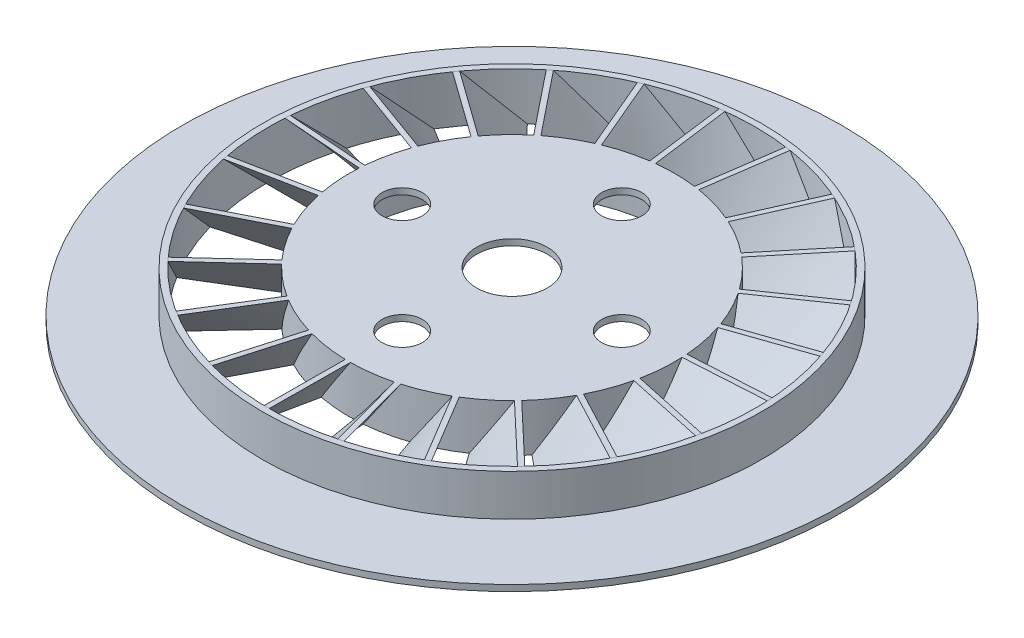
SolidWorks part; units mm, degrees
ref_plane "Front Plane" through (0, 0, 0) normal (0, 0, 1) x (1, 0, 0)
ref_plane "Top Plane" through (0, 0, 0) normal (0, 1, 0) x (1, 0, 0)
ref_plane "Right Plane" through (0, 0, 0) normal (1, 0, 0) x (0, 0, -1)
sketch "Sketch1" plane through (0, 0, 0) normal (0, 1, 0) x (1, 0, 0)
  circle A0 centre (0, 0) radius 33.25
  circle A1 centre (0, 0) radius 34.0882
  circle A2 centre (0, 0) radius 45
  circle A3 centre (0, 0) radius 22.25
  circle A4 centre (0, 0) radius 21.4118
  dimension "D1" = 66.5
  dimension "D2" = 0.8382
  dimension "D3" = 90
  dimension "D4" = 44.5
  dimension "D5" = 0.8382
extrude "Boss-Extrude1" add sketch "Sketch1" along normal blind 6.5 contours A1 A0 region at (-33.9918, 0, 0)
extrude "Boss-Extrude2" add sketch "Sketch1<3>" along normal blind 0.8382 contours A2 A1 region at (-43.7272, 0, 0)
sketch "Sketch1<3>" plane through (0, 0, 0) normal (0, 1, 0) x (1, 0, 0) same geometry as "Sketch1"
extrude "Boss-Extrude3" add sketch "Sketch1<4>" along normal blind 6.5 separate body contours A3 A4 region at (-21.6207, 0, 0)
sketch "Sketch1<4>" plane through (0, 0, 0) normal (0, 1, 0) x (1, 0, 0) same geometry as "Sketch1"
extrude "Boss-Extrude4" add sketch "Sketch1<5>" along normal blind 0.7 contours A4 region at (0, 0, 0)
sketch "Sketch1<5>" plane through (0, 0, 0) normal (0, 1, 0) x (1, 0, 0) same geometry as "Sketch1"
sketch "Sketch2" plane through (0, 0, 0) normal (0, -1, 0) x (1, 0, 0)
  line L0 (-31.9208, 9.3073) -> (-21.3278, 6.3393)
  line L1 (-33.2482, 0.35) -> (-22.2472, 0.35)
  line L2 (-33.2482, -0.35) -> (-22.2472, -0.35)
  line L3 (-32.1097, 8.6332) -> (-21.5167, 5.6652)
  line L4 (-28.226, 17.5743) -> (-18.8266, 11.8584)
  line L5 (-28.5897, 16.9762) -> (-19.1903, 11.2603)
  line L6 (-22.4378, 24.5378) -> (-14.9291, 16.498)
  line L7 (-22.9494, 24.0601) -> (-15.4407, 16.0202)
  line L8 (-14.9856, 29.6816) -> (-9.9244, 19.914)
  line L9 (-15.6071, 29.3595) -> (-10.5459, 19.592)
  line L10 (-6.4219, 32.624) -> (-4.1837, 21.8531)
  line L11 (-7.1072, 32.4815) -> (-4.869, 21.7107)
  line L12 (2.6181, 33.1468) -> (1.8674, 22.1715)
  line L13 (1.9198, 33.1945) -> (1.169, 22.2193)
  line L14 (11.4639, 31.2112) -> (7.7799, 20.8455)
  line L15 (10.8043, 31.4456) -> (7.1204, 21.0799)
  line L16 (19.4595, 26.9609) -> (13.1155, 17.9735)
  line L17 (18.8876, 27.3646) -> (12.5436, 18.3772)
  line L18 (26.0119, 20.711) -> (17.4783, 13.7685)
  line L19 (25.5701, 21.254) -> (17.0366, 14.3115)
  line L20 (30.635, 12.9251) -> (20.5449, 8.5423)
  line L21 (30.3561, 13.5671) -> (20.266, 9.1844)
  line L22 (32.9861, 4.1806) -> (22.0877, 2.6826)
  line L23 (32.8908, 4.874) -> (21.9924, 3.3761)
  line L24 (32.8908, -4.874) -> (21.9924, -3.3761)
  line L25 (32.9861, -4.1806) -> (22.0877, -2.6826)
  line L26 (30.3561, -13.5671) -> (20.266, -9.1844)
  line L27 (30.635, -12.9251) -> (20.5449, -8.5423)
  line L28 (25.5701, -21.254) -> (17.0366, -14.3115)
  line L29 (26.0119, -20.711) -> (17.4783, -13.7685)
  line L30 (18.8876, -27.3646) -> (12.5436, -18.3772)
  line L31 (19.4595, -26.9609) -> (13.1155, -17.9735)
  line L32 (10.8043, -31.4456) -> (7.1204, -21.0799)
  line L33 (11.4639, -31.2112) -> (7.7799, -20.8455)
  line L34 (1.9198, -33.1945) -> (1.169, -22.2193)
  line L35 (2.6181, -33.1468) -> (1.8674, -22.1715)
  line L36 (-7.1072, -32.4815) -> (-4.869, -21.7107)
  line L37 (-6.4219, -32.624) -> (-4.1837, -21.8531)
  line L38 (-15.6071, -29.3595) -> (-10.5459, -19.592)
  line L39 (-14.9856, -29.6816) -> (-9.9244, -19.914)
  line L40 (-22.9494, -24.0601) -> (-15.4407, -16.0202)
  line L41 (-22.4378, -24.5378) -> (-14.9291, -16.498)
  line L42 (-28.5897, -16.9762) -> (-19.1903, -11.2603)
  line L43 (-28.226, -17.5743) -> (-18.8266, -11.8584)
  line L44 (-32.1097, -8.6332) -> (-21.5167, -5.6652)
  line L45 (-31.9208, -9.3073) -> (-21.3278, -6.3393)
  circle A0 centre (0, 0) radius 33.25 construction
  circle A1 centre (0, 0) radius 22.25
  arc A2 (-21.3278, 6.3393) -> (-21.5167, 5.6652) centre (0, 0) ccw
  arc A3 (-18.8266, 11.8584) -> (-19.1903, 11.2603) centre (0, 0) ccw
  circle A5 centre (0, 0) radius 22.25 construction
  arc A6 (-31.9208, 9.3073) -> (-32.1097, 8.6332) centre (0, 0) ccw
  arc A7 (-28.226, 17.5743) -> (-28.5897, 16.9762) centre (0, 0) ccw
  arc A8 (-22.4378, 24.5378) -> (-22.9494, 24.0601) centre (0, 0) ccw
  arc A9 (-14.9291, 16.498) -> (-15.4407, 16.0202) centre (0, 0) ccw
  arc A10 (-9.9244, 19.914) -> (-10.5459, 19.592) centre (0, 0) ccw
  arc A11 (-14.9856, 29.6816) -> (-15.6071, 29.3595) centre (0, 0) ccw
  arc A12 (-6.4219, 32.624) -> (-7.1072, 32.4815) centre (0, 0) ccw
  arc A13 (-4.1837, 21.8531) -> (-4.869, 21.7107) centre (0, 0) ccw
  arc A14 (1.8674, 22.1715) -> (1.169, 22.2193) centre (0, 0) ccw
  arc A15 (2.6181, 33.1468) -> (1.9198, 33.1945) centre (0, 0) ccw
  arc A16 (11.4639, 31.2112) -> (10.8043, 31.4456) centre (0, 0) ccw
  arc A17 (7.7799, 20.8455) -> (7.1204, 21.0799) centre (0, 0) ccw
  arc A18 (13.1155, 17.9735) -> (12.5436, 18.3772) centre (0, 0) ccw
  arc A19 (19.4595, 26.9609) -> (18.8876, 27.3646) centre (0, 0) ccw
  arc A20 (26.0119, 20.711) -> (25.5701, 21.254) centre (0, 0) ccw
  arc A21 (17.4783, 13.7685) -> (17.0366, 14.3115) centre (0, 0) ccw
  arc A22 (20.5449, 8.5423) -> (20.266, 9.1844) centre (0, 0) ccw
  arc A23 (30.635, 12.9251) -> (30.3561, 13.5671) centre (0, 0) ccw
  arc A24 (32.9861, 4.1806) -> (32.8908, 4.874) centre (0, 0) ccw
  arc A25 (22.0877, 2.6826) -> (21.9924, 3.3761) centre (0, 0) ccw
  arc A26 (21.9924, -3.3761) -> (22.0877, -2.6826) centre (0, 0) ccw
  arc A27 (32.8908, -4.874) -> (32.9861, -4.1806) centre (0, 0) ccw
  arc A28 (-22.2472, 0.35) -> (-22.2472, -0.35) centre (0, 0) ccw
  arc A29 (-33.2482, 0.35) -> (-33.2482, -0.35) centre (0, 0) ccw
  arc A30 (-21.5167, -5.6652) -> (-21.3278, -6.3393) centre (0, 0) ccw
  arc A31 (-32.1097, -8.6332) -> (-31.9208, -9.3073) centre (0, 0) ccw
  arc A32 (-19.1903, -11.2603) -> (-18.8266, -11.8584) centre (0, 0) ccw
  arc A33 (-28.5897, -16.9762) -> (-28.226, -17.5743) centre (0, 0) ccw
  arc A34 (-22.9494, -24.0601) -> (-22.4378, -24.5378) centre (0, 0) ccw
  arc A35 (-15.4407, -16.0202) -> (-14.9291, -16.498) centre (0, 0) ccw
  arc A36 (-10.5459, -19.592) -> (-9.9244, -19.914) centre (0, 0) ccw
  arc A37 (-15.6071, -29.3595) -> (-14.9856, -29.6816) centre (0, 0) ccw
  arc A38 (-7.1072, -32.4815) -> (-6.4219, -32.624) centre (0, 0) ccw
  arc A39 (-4.869, -21.7107) -> (-4.1837, -21.8531) centre (0, 0) ccw
  arc A40 (1.169, -22.2193) -> (1.8674, -22.1715) centre (0, 0) ccw
  arc A41 (1.9198, -33.1945) -> (2.6181, -33.1468) centre (0, 0) ccw
  arc A42 (10.8043, -31.4456) -> (11.4639, -31.2112) centre (0, 0) ccw
  arc A43 (7.1204, -21.0799) -> (7.7799, -20.8455) centre (0, 0) ccw
  arc A44 (12.5436, -18.3772) -> (13.1155, -17.9735) centre (0, 0) ccw
  arc A45 (18.8876, -27.3646) -> (19.4595, -26.9609) centre (0, 0) ccw
  arc A46 (25.5701, -21.254) -> (26.0119, -20.711) centre (0, 0) ccw
  arc A47 (17.0366, -14.3115) -> (17.4783, -13.7685) centre (0, 0) ccw
  arc A48 (20.266, -9.1844) -> (20.5449, -8.5423) centre (0, 0) ccw
  arc A49 (30.3561, -13.5671) -> (30.635, -12.9251) centre (0, 0) ccw
  point P106 (0, 0)
  dimension "D3" = 0.7
  dimension "D1" = 0
  dimension "D4" = 23
sketch "Sketch3" plane through (0, 6.5, 0) normal (0, 1, 0) x (1, 0, 0)
  line L0 (0, 0) -> (-32.6054, -6.5152) construction
  line L1 (0, 0) -> (-15.6581, 0) construction
  line L2 (-21.8846, -4.016) -> (-32.6722, -6.1716)
  line L3 (-21.7474, -4.7025) -> (-32.535, -6.8581)
  line L4 (-22.1565, 2.0373) -> (-33.1257, 2.8721)
  line L5 (-22.2097, 1.3393) -> (-33.1788, 2.1741)
  line L6 (-20.7853, 7.9395) -> (-31.1225, 11.7028)
  line L7 (-21.0247, 7.2817) -> (-31.3619, 11.045)
  line L8 (-17.8724, 13.2529) -> (-26.811, 19.6656)
  line L9 (-18.2805, 12.6841) -> (-27.219, 19.0968)
  line L10 (-13.6341, 17.5833) -> (-20.511, 26.1698)
  line L11 (-14.1805, 17.1457) -> (-21.0574, 25.7322)
  line L12 (-8.3846, 20.6097) -> (-12.6899, 30.7332)
  line L13 (-9.0288, 20.3358) -> (-13.3341, 30.4592)
  line L14 (-2.5132, 22.1076) -> (-3.9276, 33.0172)
  line L15 (-3.2074, 22.0176) -> (-4.6218, 32.9272)
  line L16 (3.5445, 21.9659) -> (5.126, 32.8525)
  line L17 (2.8518, 22.0665) -> (4.4332, 32.9531)
  line L18 (9.3394, 20.195) -> (13.7994, 30.2513)
  line L19 (8.6995, 20.4788) -> (13.1595, 30.5351)
  line L20 (14.4416, 16.9264) -> (21.4494, 25.4064)
  line L21 (13.902, 17.3723) -> (20.9098, 25.8524)
  line L22 (18.4728, 12.4024) -> (27.5085, 18.6773)
  line L23 (18.0735, 12.9774) -> (27.1093, 19.2523)
  line L24 (21.1339, 6.9586) -> (31.5275, 10.563)
  line L25 (20.9045, 7.6199) -> (31.2982, 11.2244)
  line L26 (22.2276, 0.9987) -> (33.2083, 1.6653)
  line L27 (22.1852, 1.6974) -> (33.1659, 2.364)
  line L28 (21.6728, -5.0353) -> (32.4261, -7.356)
  line L29 (21.8204, -4.351) -> (32.5738, -6.6717)
  line L30 (19.5106, -10.6958) -> (29.239, -15.8316)
  line L31 (19.8374, -10.0768) -> (29.5658, -15.2126)
  line L32 (15.9014, -15.563) -> (23.8835, -23.1332)
  line L33 (16.3831, -15.0551) -> (24.3652, -22.6252)
  line L34 (11.1129, -19.2761) -> (16.7565, -28.719)
  line L35 (11.7137, -18.917) -> (17.3574, -28.3599)
  line L36 (5.5001, -21.5595) -> (8.3869, -32.1749)
  line L37 (6.1756, -21.3758) -> (9.0623, -31.9912)
  line L38 (-0.5205, -22.2439) -> (-0.6048, -33.2445)
  line L39 (0.1795, -22.2493) -> (0.0952, -33.2499)
  line L40 (-6.5025, -21.2786) -> (-9.5516, -31.8485)
  line L41 (-5.83, -21.4726) -> (-8.8791, -32.0425)
  line L42 (-12.0023, -18.7352) -> (-17.7901, -28.0905)
  line L43 (-11.407, -19.1035) -> (-17.1948, -28.4588)
  line L44 (-16.6119, -14.8023) -> (-24.7091, -22.2491)
  line L45 (-16.1381, -15.3175) -> (-24.2352, -22.7644)
  line L46 (-19.9895, -9.7715) -> (-29.7956, -14.7576)
  line L47 (-19.6722, -10.3955) -> (-29.4783, -15.3816)
  circle A0 centre (0, 0) radius 33.25 construction
  circle A1 centre (0, 0) radius 22.25 construction
  arc A2 (-32.6722, -6.1716) -> (-32.535, -6.8581) centre (0, 0) ccw
  arc A3 (-21.8846, -4.016) -> (-21.7474, -4.7025) centre (0, 0) ccw
  arc A4 (-22.1565, 2.0373) -> (-22.2097, 1.3393) centre (0, 0) ccw
  arc A5 (-33.1257, 2.8721) -> (-33.1788, 2.1741) centre (0, 0) ccw
  arc A6 (-20.7853, 7.9395) -> (-21.0247, 7.2817) centre (0, 0) ccw
  arc A7 (-31.1225, 11.7028) -> (-31.3619, 11.045) centre (0, 0) ccw
  arc A8 (-17.8724, 13.2529) -> (-18.2805, 12.6841) centre (0, 0) ccw
  arc A9 (-26.811, 19.6656) -> (-27.219, 19.0968) centre (0, 0) ccw
  arc A10 (-13.6341, 17.5833) -> (-14.1805, 17.1457) centre (0, 0) ccw
  arc A11 (-20.511, 26.1698) -> (-21.0574, 25.7322) centre (0, 0) ccw
  arc A12 (-8.3846, 20.6097) -> (-9.0288, 20.3358) centre (0, 0) ccw
  arc A13 (-12.6899, 30.7332) -> (-13.3341, 30.4592) centre (0, 0) ccw
  arc A14 (-2.5132, 22.1076) -> (-3.2074, 22.0176) centre (0, 0) ccw
  arc A15 (-3.9276, 33.0172) -> (-4.6218, 32.9272) centre (0, 0) ccw
  arc A16 (3.5445, 21.9659) -> (2.8518, 22.0665) centre (0, 0) ccw
  arc A17 (5.126, 32.8525) -> (4.4332, 32.9531) centre (0, 0) ccw
  arc A18 (9.3394, 20.195) -> (8.6995, 20.4788) centre (0, 0) ccw
  arc A19 (13.7994, 30.2513) -> (13.1595, 30.5351) centre (0, 0) ccw
  arc A20 (14.4416, 16.9264) -> (13.902, 17.3723) centre (0, 0) ccw
  arc A21 (21.4494, 25.4064) -> (20.9098, 25.8524) centre (0, 0) ccw
  arc A22 (18.4728, 12.4024) -> (18.0735, 12.9774) centre (0, 0) ccw
  arc A23 (27.5085, 18.6773) -> (27.1093, 19.2523) centre (0, 0) ccw
  arc A24 (21.1339, 6.9586) -> (20.9045, 7.6199) centre (0, 0) ccw
  arc A25 (31.5275, 10.563) -> (31.2982, 11.2244) centre (0, 0) ccw
  arc A26 (22.2276, 0.9987) -> (22.1852, 1.6974) centre (0, 0) ccw
  arc A27 (33.2083, 1.6653) -> (33.1659, 2.364) centre (0, 0) ccw
  arc A28 (21.6728, -5.0353) -> (21.8204, -4.351) centre (0, 0) ccw
  arc A29 (32.4261, -7.356) -> (32.5738, -6.6717) centre (0, 0) ccw
  arc A30 (19.5106, -10.6958) -> (19.8374, -10.0768) centre (0, 0) ccw
  arc A31 (29.239, -15.8316) -> (29.5658, -15.2126) centre (0, 0) ccw
  arc A32 (15.9014, -15.563) -> (16.3831, -15.0551) centre (0, 0) ccw
  arc A33 (23.8835, -23.1332) -> (24.3652, -22.6252) centre (0, 0) ccw
  arc A34 (11.1129, -19.2761) -> (11.7137, -18.917) centre (0, 0) ccw
  arc A35 (16.7565, -28.719) -> (17.3574, -28.3599) centre (0, 0) ccw
  arc A36 (5.5001, -21.5595) -> (6.1756, -21.3758) centre (0, 0) ccw
  arc A37 (8.3869, -32.1749) -> (9.0623, -31.9912) centre (0, 0) ccw
  arc A38 (-0.5205, -22.2439) -> (0.1795, -22.2493) centre (0, 0) ccw
  arc A39 (-0.6048, -33.2445) -> (0.0952, -33.2499) centre (0, 0) ccw
  arc A40 (-6.5025, -21.2786) -> (-5.83, -21.4726) centre (0, 0) ccw
  arc A41 (-9.5516, -31.8485) -> (-8.8791, -32.0425) centre (0, 0) ccw
  arc A42 (-12.0023, -18.7352) -> (-11.407, -19.1035) centre (0, 0) ccw
  arc A43 (-17.7901, -28.0905) -> (-17.1948, -28.4588) centre (0, 0) ccw
  arc A44 (-16.6119, -14.8023) -> (-16.1381, -15.3175) centre (0, 0) ccw
  arc A45 (-24.7091, -22.2491) -> (-24.2352, -22.7644) centre (0, 0) ccw
  arc A46 (-19.9895, -9.7715) -> (-19.6722, -10.3955) centre (0, 0) ccw
  arc A47 (-29.7956, -14.7576) -> (-29.4783, -15.3816) centre (0, 0) ccw
  point P101 (0, 0)
  dimension "D1" = 11.3
  dimension "D2" = 0.35
  dimension "D3" = 0.35
  dimension "D4" = 23
loft "Loft1" add section "Sketch2" section "Sketch3" connector at (-32.1097, 0, 8.6332) connector at (-29.7956, 6.5, 14.7576)
pattern_circular "CirPattern1" count 23 over 360 about axis through (0, 6.5, 0) along (0, -1, 0) of "Loft1"
sketch "Sketch4" plane through (0, 6.5, 0) normal (0, 1, 0) x (1, 0, 0)
  circle A0 centre (0, 0) radius 21.55
  dimension "D1" = 43.1
extrude "Boss-Extrude5" add sketch "Sketch4" against normal blind 0.8382
sketch "Sketch6" plane through (0, 0, 0) normal (0, -1, 0) x (1, 0, 0)
  line L0 (0, 0) -> (0, 14.9949) construction
  line L1 (0, 0) -> (14.9949, 0) construction
  line L2 (0, 0) -> (0, -14.9949) construction
  line L3 (0, 0) -> (-14.9949, 0) construction
  point P9 (0, 0)
  dimension "D1" = 14.9949
  dimension "D2" = 4
hole_wizard "CBORE for M5 Hex Head Bolt1" positions "3DSketch4" profile "Sketch7" counterbore size "M5" standard "ANSI Metric" end condition through all
sketch3d "3DSketch4"
  point P0 (0, 0, 14.9949)
  point P3 (14.9949, 0, 0)
  point P6 (0, 0, -14.9949)
  point P9 (-14.9949, 0, 0)
sketch "Sketch7" plane through (0, 0, 14.9949) normal (1, 0, 0) x (0, 0, -1)
  line L0 (0, 0) -> (0, 6.5001)
  line L1 (0, 6.5001) -> (2.75, 6.5001)
  line L3 (2.75, 6.5001) -> (2.75, 3.58)
  line L4 (2.75, 3.58) -> (6.12, 3.58)
  line L5 (6.12, 3.58) -> (6.12, 0)
  line L7 (6.12, 0) -> (0, 0)
  line L11 (0, -6.35) -> (0, 107.95) construction
  dimension "Thru Hole Dia." = 5.5
  dimension "Thru Hole Depth" = 6.5001
  dimension "C'Bore Dia." = 12.24
  dimension "C'Bore Depth" = 3.58
sketch "Sketch8" plane through (0, 0, 0) normal (0, -1, 0) x (1, 0, 0)
  circle A0 centre (0, 0) radius 21.39
  arc A1 (22.0877, -2.6826) -> (22.0877, 2.6826) centre (0, 0) ccw construction
  circle A2 centre (0, 0) radius 22.25
  dimension "D1" = 0.86
  dimension "D2" = 44.5
extrude "Cut-Extrude1" cut sketch "Sketch8" against normal blind 1.5 contours A0 region at (0, 0, 0)
extrude "Boss-Extrude6" add sketch "Sketch8<2>" against normal up to surface (6.5 mm away) up to face at (0, 6.5, 17.7449)
sketch "Sketch8<2>" plane through (0, 0, 0) normal (0, -1, 0) x (1, 0, 0) same geometry as "Sketch8"
sketch "Sketch9" plane through (0, 5.6618, 0) normal (0, -1, 0) x (1, 0, 0)
  circle A0 centre (0, 0) radius 4.826
  dimension "D1" = 9.652
extrude "Cut-Extrude2" cut sketch "Sketch9" against normal blind 2.54
